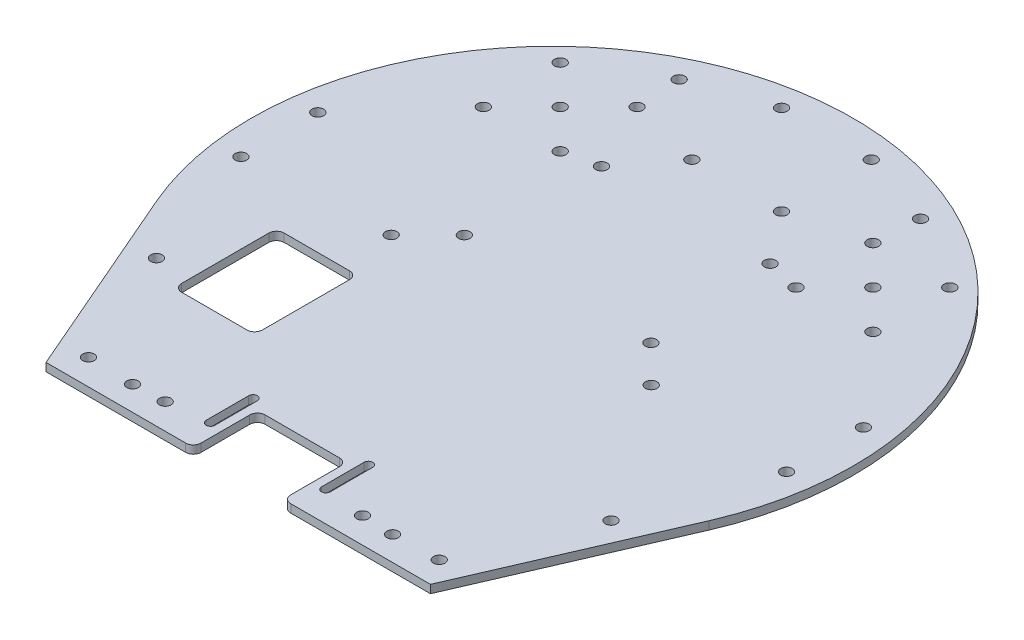
SolidWorks part; units mm, degrees
ref_plane "Front Plane" through (0, 0, 0) normal (0, 0, 1) x (1, 0, 0)
ref_plane "Top Plane" through (0, 0, 0) normal (0, 1, 0) x (1, 0, 0)
ref_plane "Right Plane" through (0, 0, 0) normal (1, 0, 0) x (0, 0, -1)
sketch "Sketch1" plane through (0, 0, 0) normal (0, 1, 0) x (1, 0, 0)
  circle A0 centre (0, 0) radius 117.5
  dimension "D1" = 235
extrude "Boss-Extrude1" add sketch "Sketch1" along normal blind 3.175
sketch "Sketch4" plane through (0, 0, 0) normal (0, 1, 0) x (1, 0, 0)
  line L2 (0, 0) -> (0, -53.2962) construction
  line L5 (107.8261, -46.6881) -> (75, -122.5)
  line L6 (75, -122.5) -> (-75, -122.5)
  line L7 (-75, -122.5) -> (-107.8261, -46.6881)
  line L8 (-107.8261, -46.6881) -> (107.8261, -46.6881)
  line L9 (0, -122.5) -> (0, -117.5) construction
  circle A3 centre (0, 0) radius 117.5 construction
  circle A4 centre (0, 0) radius 117.5 construction
  dimension "D1" = 150
  dimension "D2" = 5
extrude "Boss-Extrude2" add sketch "Sketch4" along normal up to surface (3.175 mm away) contours L5 | L8 L7 L6 L5 region at (0, 0, 82.3254) up to face at (0, 3.175, 117.5)
sketch "Sketch5" plane through (0, 0, 0) normal (0, 1, 0) x (1, 0, 0)
  line L0 (75, 117.5) -> (-0.1661, 117.5)
  line L1 (75, 117.5) -> (106.5777, 49.4717)
  line L2 (0, 0) -> (0, 46.0662) construction
  line L3 (-75, 117.5) -> (-0.1661, 117.5)
  line L4 (-75, 117.5) -> (-106.5777, 49.4717)
  circle A0 centre (0, 0) radius 117.5 construction
  arc A1 (106.5777, 49.4717) -> (-106.5777, 49.4717) centre (0, 0) ccw
  dimension "D1" = 150
extrude "Boss-Extrude3" [suppressed] add sketch "Sketch5" along normal up to surface (3.175 mm away) contours A1 L1 L0 | A1 L0 L3 L4 up to face at (0, 3.175, 43.547)
hole_wizard "#8 Clearance Hole1" positions "Sketch6" profile "Sketch7" hole size "#8" standard "ANSI Inch" end condition through all
sketch "Sketch6" plane through (0, 3.175, 0) normal (0, 1, 0) x (1, 0, 0)
  circle A0 centre (47.0917, 96.6365) radius 1.7272 construction
  circle A1 centre (17.5, 107) radius 1.7272 construction
  circle A2 centre (32.9, 52.1319) radius 1.7272 construction
  circle A3 centre (17.5, 72) radius 1.7272 construction
  circle A4 centre (-17.5, 72) radius 1.7272 construction
  circle A5 centre (-17.5, 107) radius 1.7272 construction
  circle A6 centre (-47.0917, 96.6365) radius 1.7272 construction
  circle A7 centre (-32.9, 52.1319) radius 1.7272 construction
  circle A8 centre (-106.4483, 15) radius 1.7272 construction
  circle A9 centre (-36.4, 2.1319) radius 1.7272 construction
  circle A10 centre (36.4, 2.1319) radius 1.7272 construction
  circle A11 centre (50.74, -12.09) radius 1.7 construction
  circle A12 centre (-50.74, -12.09) radius 1.7 construction
  circle A13 centre (-106.4483, -15) radius 1.7272 construction
  circle A14 centre (-88.6902, -65.7156) radius 1.7272 construction
  circle A15 centre (-68.4328, -112.5) radius 1.7272 construction
  circle A16 centre (-50.74, -113) radius 1.7 construction
  circle A17 centre (50.74, -113) radius 1.7 construction
  circle A18 centre (-38.5, -112.5) radius 1.7272 construction
  circle A19 centre (38.5, -112.5) radius 1.7272 construction
  circle A20 centre (68.4328, -112.5) radius 1.7272 construction
  circle A21 centre (88.6902, -65.7156) radius 1.7272 construction
  circle A22 centre (106.4483, -15) radius 1.7272 construction
  circle A23 centre (106.4483, 15) radius 1.7272 construction
  circle A24 centre (47.0917, 96.6365) radius 1.7272
  circle A25 centre (17.5, 107) radius 1.7272
  circle A26 centre (32.9, 52.1319) radius 1.7272
  circle A27 centre (17.5, 72) radius 1.7272
  circle A28 centre (-17.5, 72) radius 1.7272
  circle A29 centre (-17.5, 107) radius 1.7272
  circle A30 centre (-47.0917, 96.6365) radius 1.7272
  circle A31 centre (-32.9, 52.1319) radius 1.7272
  circle A32 centre (-106.4483, 15) radius 1.7272
  circle A33 centre (-36.4, 2.1319) radius 1.7272
  circle A34 centre (36.4, 2.1319) radius 1.7272
  circle A35 centre (50.74, -12.09) radius 1.7
  circle A36 centre (-50.74, -12.09) radius 1.7
  circle A37 centre (-106.4483, -15) radius 1.7272
  circle A38 centre (-88.6902, -65.7156) radius 1.7272
  circle A39 centre (-68.4328, -112.5) radius 1.7272
  circle A40 centre (-50.74, -113) radius 1.7
  circle A41 centre (50.74, -113) radius 1.7
  circle A42 centre (-38.5, -112.5) radius 1.7272
  circle A43 centre (38.5, -112.5) radius 1.7272
  circle A44 centre (68.4328, -112.5) radius 1.7272
  circle A45 centre (88.6902, -65.7156) radius 1.7272
  circle A46 centre (106.4483, -15) radius 1.7272
  circle A47 centre (106.4483, 15) radius 1.7272
  point P1 (47.0917, 96.6365)
  point P3 (17.5, 107)
  point P5 (32.9, 52.1319)
  point P7 (17.5, 72)
  point P9 (-17.5, 72)
  point P11 (-17.5, 107)
  point P13 (-47.0917, 96.6365)
  point P15 (-32.9, 52.1319)
  point P17 (-106.4483, 15)
  point P19 (-36.4, 2.1319)
  point P21 (36.4, 2.1319)
  point P23 (50.74, -12.09)
  point P25 (-50.74, -12.09)
  point P27 (-106.4483, -15)
  point P29 (-88.6902, -65.7156)
  point P31 (-68.4328, -112.5)
  point P33 (-50.74, -113)
  point P35 (50.74, -113)
  point P37 (-38.5, -112.5)
  point P39 (38.5, -112.5)
  point P41 (68.4328, -112.5)
  point P43 (88.6902, -65.7156)
  point P45 (106.4483, -15)
  point P47 (106.4483, 15)
sketch "Sketch7" plane through (47.0917, 3.175, -96.6365) normal (1, 0, 0) x (0, 0, 1)
  line L0 (0, 0) -> (0, 3.175)
  line L1 (0, 3.175) -> (2.2479, 3.175)
  line L2 (2.2479, 3.175) -> (2.2479, 0)
  line L5 (2.2479, 0) -> (0, 0)
  line L11 (0, -6.35) -> (0, 107.95) construction
  dimension "Thru Hole Dia." = 4.4958
  dimension "Thru Hole Depth" = 3.175
sketch "Sketch9" plane through (0, 3.175, 0) normal (0, 1, 0) x (1, 0, 0)
  line L0 (75, -122.5) -> (-75, -122.5) construction
  line L1 (-17.5, -122.5) -> (17.5, -122.5)
  line L2 (-17.5, -122.5) -> (-17.5, -97.5)
  line L3 (-17.5, -97.5) -> (17.5, -97.5)
  line L4 (17.5, -122.5) -> (17.5, -97.5)
  point P6 (0, -122.5)
  dimension "D1" = 25
  dimension "D2" = 35
extrude "Cut-Extrude2" cut sketch "Sketch9" against normal through all
hole_wizard "M3 Clearance Slot2" positions "Sketch13" profile "Sketch14" size "M3" standard "ANSI Metric" slot yes end condition through all
sketch "Sketch13" plane through (0, 3.175, 0) normal (0, 1, 0) x (1, 0, 0)
  line L0 (-22.5, -112.5) -> (-22.5, -92.5) construction
  line L1 (-22.5, -102.5) -> (22.5, -102.5) construction
  line L3 (0, -102.5) -> (0, 0) construction
  line L6 (-17.5, -122.5) -> (-75, -122.5) construction
  point P0 (-22.5, -102.5)
  point P4 (22.5, -102.5)
  dimension "D1" = 20
  dimension "D2" = 45
  dimension "D3" = 10
sketch "Sketch14" plane through (-22.5, 3.175, 102.5) normal (1, 0, 0) x (0, 0, 1)
  line L0 (0, 0) -> (0, 3.175)
  line L1 (0, 3.175) -> (1.7, 3.175)
  line L2 (1.7, 3.175) -> (1.7, 0)
  line L5 (1.7, 0) -> (0, 0)
  line L11 (0, -6.35) -> (0, 107.95) construction
  dimension "Thru Hole Dia." = 3.4
  dimension "Thru Hole Depth" = 3.175
sketch "Sketch15" plane through (0, 3.175, 0) normal (0, 1, 0) x (1, 0, 0)
  line L0 (-43.74, -44.835) -> (-43.74, -59.835) construction
  line L1 (-75.24, -32.335) -> (-43.74, -32.335)
  line L2 (-75.24, -32.335) -> (-75.24, -72.335)
  line L3 (-75.24, -72.335) -> (-43.74, -72.335)
  line L4 (-43.74, -32.335) -> (-43.74, -72.335)
  line L5 (-43.74, -44.835) -> (-43.74, -59.835) construction
  line L6 (-55.24, -12.09) -> (-55.24, -41.835) construction
  line L7 (-55.24, -12.09) -> (-55.24, -41.835) construction
  point P6 (-43.74, -52.335)
  dimension "D1" = 40
  dimension "D2" = 20
extrude "Cut-Extrude3" cut sketch "Sketch15" against normal through all
hole_wizard "#8 Clearance Hole2" positions "Sketch16" profile "Sketch17" hole size "#8" standard "ANSI Inch" end condition through all
sketch "Sketch16" plane through (0, 3.175, 0) normal (0, 1, 0) x (1, 0, 0)
  line L8 (-76, 49.1319) -> (-46, 49.1319)
  line L9 (-46, 49.1319) -> (-46, 79.1319)
  line L10 (-46, 79.1319) -> (-76, 79.1319)
  line L11 (-76, 79.1319) -> (-76, 49.1319)
  line L12 (-76, 49.1319) -> (-46, 49.1319)
  line L13 (-46, 49.1319) -> (-46, 79.1319)
  line L14 (-46, 79.1319) -> (-76, 79.1319)
  line L15 (-76, 79.1319) -> (-76, 49.1319)
  line L24 (46, 49.1319) -> (76, 49.1319)
  line L25 (76, 49.1319) -> (76, 79.1319)
  line L26 (76, 79.1319) -> (46, 79.1319)
  line L27 (46, 79.1319) -> (46, 49.1319)
  line L28 (46, 49.1319) -> (76, 49.1319)
  line L29 (76, 49.1319) -> (76, 79.1319)
  line L30 (76, 79.1319) -> (46, 79.1319)
  line L31 (46, 79.1319) -> (46, 49.1319)
  line L32 (-76, 79.1319) -> (-46, 49.1319)
  line L34 (46, 79.1319) -> (76, 49.1319)
  point P9 (-76, 49.1319)
  point P10 (-46, 49.1319)
  point P12 (-46, 79.1319)
  point P13 (-76, 79.1319)
  point P25 (46, 49.1319)
  point P26 (76, 49.1319)
  point P28 (76, 79.1319)
  point P29 (46, 79.1319)
  point P65 (-61, 64.1319)
  point P67 (61, 64.1319)
  dimension "D1" = 0
  dimension "D2" = 0
sketch "Sketch17" plane through (-76, 3.175, -49.1319) normal (1, 0, 0) x (0, 0, 1)
  line L0 (0, 0) -> (0, 3.175)
  line L1 (0, 3.175) -> (2.2479, 3.175)
  line L2 (2.2479, 3.175) -> (2.2479, 0)
  line L5 (2.2479, 0) -> (0, 0)
  line L11 (0, -6.35) -> (0, 107.95) construction
  dimension "Thru Hole Dia." = 4.4958
  dimension "Thru Hole Depth" = 3.175
fillet "Fillet1" radius 3 4 edges at (-75.24, 1.5875, 72.335) (-75.24, 1.5875, 32.335) (-43.74, 1.5875, 32.335) (-43.74, 1.5875, 72.335)
fillet "Fillet2" radius 3 4 edges at (17.5, 1.5875, 97.5) (17.5, 1.5875, 122.5) (-17.5, 1.5875, 122.5) (-17.5, 1.5875, 97.5)
